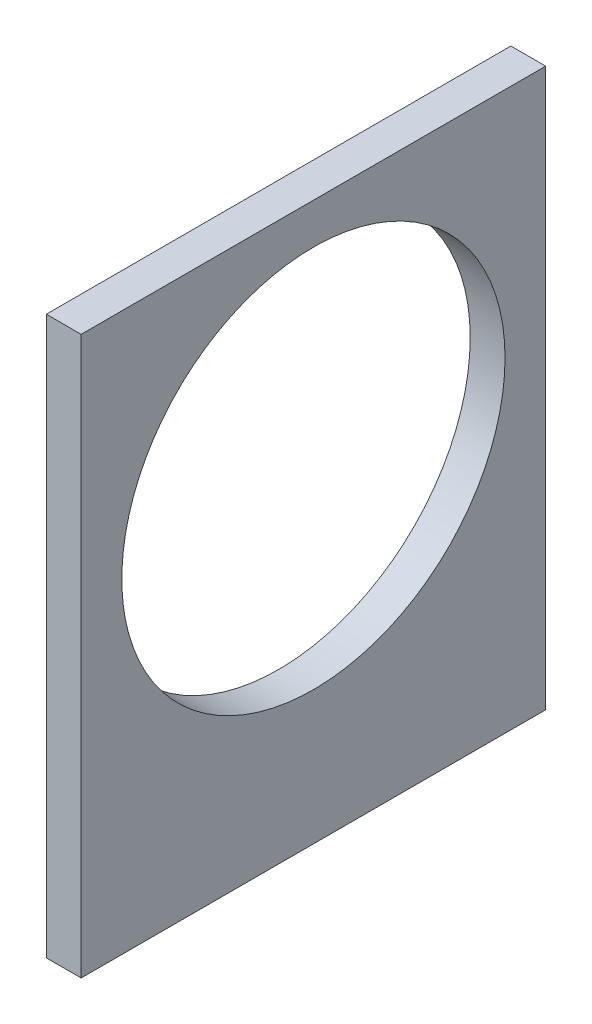
SolidWorks part; units mm, degrees
material "6061-T6 (SS)"
ref_plane "Front Plane" through (0, 0, 0) normal (0, 0, 1) x (1, 0, 0)
ref_plane "Top Plane" through (0, 0, 0) normal (0, 1, 0) x (1, 0, 0)
ref_plane "Right Plane" through (0, 0, 0) normal (1, 0, 0) x (0, 0, -1)
sketch "Sketch4" plane through (0, 0, 0) normal (1, 0, 0) x (0, 0, -1)
  line L1 (31.75, 38.1) -> (-31.75, 38.1)
  line L2 (31.75, 38.1) -> (31.75, -38.1)
  line L3 (31.75, -38.1) -> (-31.75, -38.1)
  line L4 (-31.75, 38.1) -> (-31.75, -38.1)
  line L5 (31.75, 38.1) -> (-31.75, -38.1) construction
  line L6 (31.75, -38.1) -> (-31.75, 38.1) construction
  circle A0 centre (0, 6.35) radius 26.1938
  point P0 (0, 0)
  dimension "D3" = 52.3875
  dimension "D1" = 31.75
  dimension "D2" = 63.5
  dimension "D4" = 76.2
extrude "Boss-Extrude2" add sketch "Sketch4" along normal blind 4.7625
hole_wizard "#6-32 Tapped Hole3" positions "Sketch9" profile "Sketch8" tap size "#6-32" standard "ANSI Inch"
sketch "Sketch9" plane through (0, -38.1, 0) normal (0, -1, 0) x (-1, 0, 0)
  line L0 (-4.7625, -31.75) -> (0, -31.75) construction
  line L1 (-4.7625, 31.75) -> (0, 31.75) construction
  point P0 (-2.3813, -28.575)
  point P2 (-2.3813, 28.575)
  point P10 (-2.3813, -31.75)
  dimension "D1" = 3.175
  dimension "D2" = 3.175
cosmetic thread "Hole Thread5" parameters "D1"=12.7, "D2"=3.5052
cosmetic thread "Hole Thread6" parameters "D1"=12.7, "D2"=3.5052
sketch "Sketch8" plane through (2.3813, -38.1, 28.575) normal (1, 0, 0) x (0, 0, -1)
  line L0 (0, 0) -> (0, 17.4751)
  line L1 (0, 17.4751) -> (1.3525, 16.6624)
  line L2 (1.3525, 16.6624) -> (1.3525, 0)
  line L5 (1.3525, 0) -> (0, 0)
  line L10 (0, 17.4751) -> (-1.3526, 16.6624) construction
  line L11 (0, -6.35) -> (0, 107.95) construction
  dimension "Tap Drill Dia." = 2.7051
  dimension "Tap Drill Depth" = 16.6624
  dimension "Drill Angle" = 118
